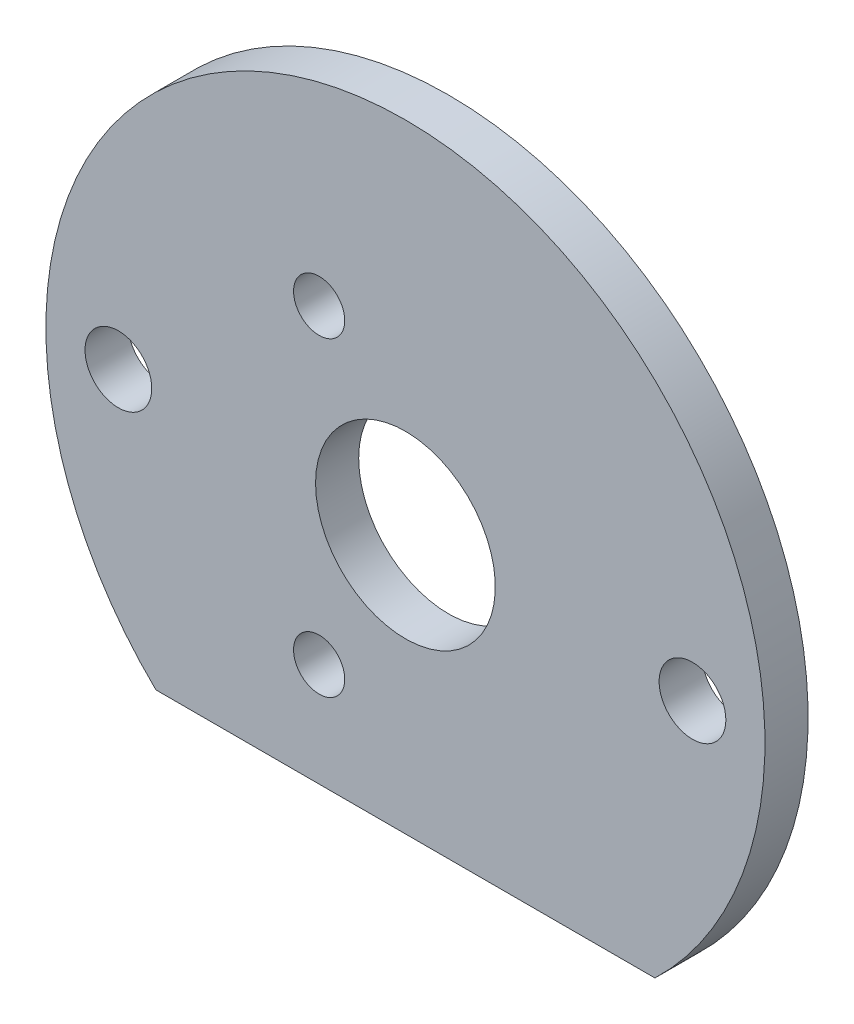
SolidWorks part; units mm, degrees
material "Cast Alloy Steel"
ref_plane "Front Plane" through (0, 0, 0) normal (0, 0, 1) x (1, 0, 0)
ref_plane "Top Plane" through (0, 0, 0) normal (0, 1, 0) x (1, 0, 0)
ref_plane "Right Plane" through (0, 0, 0) normal (1, 0, 0) x (0, 0, -1)
sketch "Sketch1" plane through (0, 0, 0) normal (0, 0, 1) x (1, 0, 0)
  circle A0 centre (0, 0) radius 15.875
  circle A1 centre (0, 0) radius 3.9688
  dimension "D1" = 7.9375
  dimension "D2" = 31.75
extrude "Boss-Extrude1" add sketch "Sketch1" along normal blind 1.905
hole_wizard "MotorClearanceHoles" positions "Sketch5" profile "Sketch4" hole size "#4" standard "ANSI Inch" end condition through all
sketch "Sketch5" plane through (0, 0, 1.905) normal (0, 0, 1) x (1, 0, 0)
  line L0 (0, 0) -> (0, 12.3097) construction
  point P0 (-12.6746, 0)
  point P2 (12.6746, 0)
  dimension "D1" = 25.3492
sketch "Sketch4" plane through (-12.6746, 0, 1.905) normal (1, 0, 0) x (0, -1, 0)
  line L0 (0, 0) -> (0, 1.905)
  line L1 (0, 1.905) -> (1.4732, 1.905)
  line L2 (1.4732, 1.905) -> (1.4732, 0)
  line L5 (1.4732, 0) -> (0, 0)
  line L11 (0, -6.35) -> (0, 107.95) construction
  dimension "Thru Hole Dia." = 2.9464
  dimension "Thru Hole Depth" = 1.905
hole_wizard "EncoderSetScrews" positions "Sketch7" profile "Sketch6" tap size "#4-40" standard "ANSI Inch" end condition through all
sketch "Sketch7" plane through (0, 0, 1.905) normal (0, 0, 1) x (1, 0, 0)
  line L0 (-21.019, 0) -> (-19.6675, 0) construction
  point P0 (-3.81, 6.858)
  point P2 (-3.81, -6.858)
  dimension "D1" = 13.716
  dimension "D2" = 3.81
sketch "Sketch6" plane through (-3.81, 6.858, 1.905) normal (1, 0, 0) x (0, -1, 0)
  line L0 (0, 0) -> (0, 1.905)
  line L1 (0, 1.905) -> (1.1303, 1.905)
  line L2 (1.1303, 1.905) -> (1.1303, 0)
  line L5 (1.1303, 0) -> (0, 0)
  line L11 (0, -6.35) -> (0, 107.95) construction
  dimension "Thru Tap Drill Dia." = 2.2606
  dimension "Thru Tap Drill Depth" = 1.905
cosmetic thread "Hole Thread1" parameters "D2"=2.8448
cosmetic thread "Hole Thread2" parameters "D2"=2.8448
sketch "Sketch8" plane through (0, 0, 1.905) normal (0, 0, 1) x (1, 0, 0)
  line L0 (-11.0168, -11.43) -> (11.0168, -11.43)
  circle A1 centre (0, 0) radius 15.875
  arc A2 (-11.0168, -11.43) -> (11.0168, -11.43) centre (0, 0) ccw
  dimension "D2" = 11.43
  dimension "D1" = 0
extrude "LinActCutaway" cut sketch "Sketch8" against normal through all
